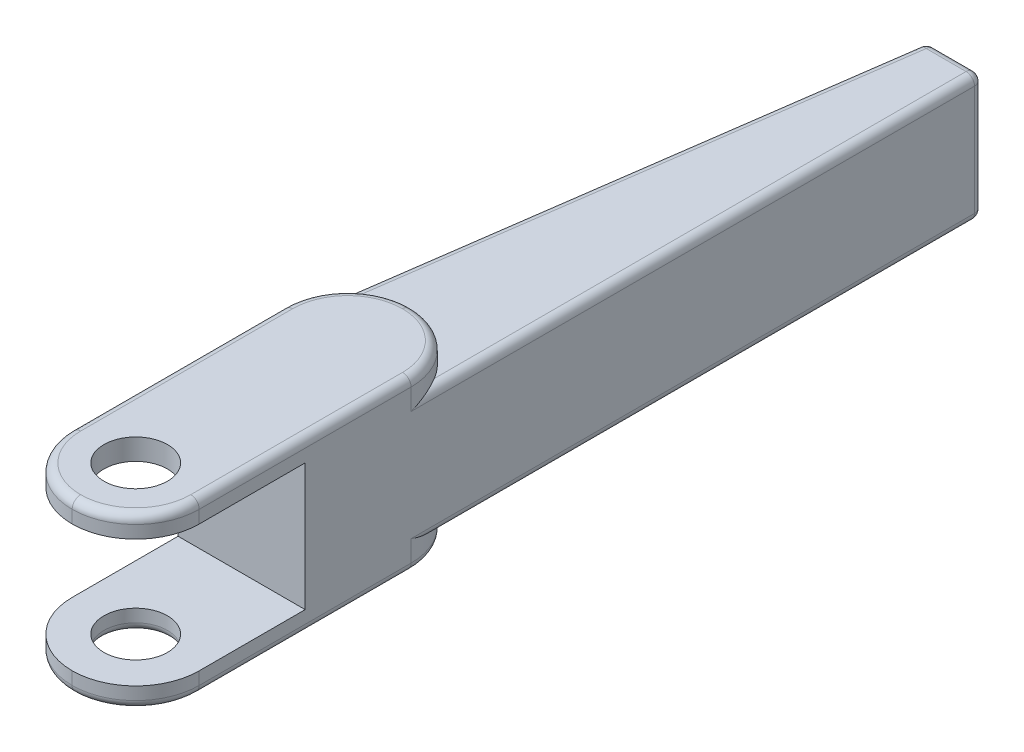
SolidWorks part; units mm, degrees
ref_plane "Front Plane" through (0, 0, 0) normal (0, 0, 1) x (1, 0, 0)
ref_plane "Top Plane" through (0, 0, 0) normal (0, 1, 0) x (1, 0, 0)
ref_plane "Right Plane" through (0, 0, 0) normal (1, 0, 0) x (0, 0, -1)
sketch "Sketch2" plane through (0, 0, 0) normal (0, 0, 1) x (1, 0, 0)
  line L1 (15, 15) -> (-15, 15)
  line L2 (15, 15) -> (15, -15)
  line L3 (15, -15) -> (-15, -15)
  line L4 (-15, 15) -> (-15, -15)
  line L5 (15, 15) -> (-15, -15) construction
  line L6 (15, -15) -> (-15, 15) construction
  point P0 (0, 0)
  dimension "D1" = 30
  dimension "D2" = 30
extrude "Boss-Extrude1" add sketch "Sketch2" along normal blind 160
sketch "Sketch3" plane through (0, 0, 160) normal (0, 0, 1) x (1, 0, 0)
  line L0 (15, 15) -> (-15, 15) construction
  line L1 (15, -20) -> (-15, -20)
  line L2 (15, -20) -> (15, 20)
  line L3 (15, 20) -> (-15, 20)
  line L4 (-15, -20) -> (-15, 20)
  line L5 (15, -20) -> (-15, 20) construction
  line L6 (15, 20) -> (-15, -20) construction
  point P0 (0, 0)
  line M6 (-15, -15) -> (15, -15)
  line M8 (15, 15) -> (-15, 15)
  dimension "D1" = 40
extrude "Boss-Extrude2" add sketch "Sketch3" against normal mid plane 80 contours L4 L2 L3 M8 | L4 L1 L2 M6 region at (0, -17.5, 160) region at (0, 17.5, 160)
fillet "Fillet1" radius 15 8 edges at (15, -17.5, 120) (-15, -17.5, 120) (15, -17.5, 200) (-15, -17.5, 200) (-15, 17.5, 120) (15, 17.5, 120) (-15, 17.5, 200) (15, 17.5, 200)
sketch "Sketch4" plane through (0, 20, 0) normal (0, 1, 0) x (1, 0, 0)
  line L0 (0, -200) -> (0, -185) construction
  line L1 (0, -185) -> (15, -185) construction
  circle A0 centre (0, -185) radius 7.5
  dimension "D1" = 15
extrude "Cut-Extrude1" cut sketch "Sketch4" against normal blind 80
chamfer "Chamfer1" distance 120 angle 8 1 edges at (-15, 0, 0) first distance on face at (-15, 0, 133.3333)
fillet "Fillet2" radius 2 21 edges at (10.6066, 20, 124.3934) (15, 20, 160) (10.6066, 20, 195.6066) (-10.6066, 20, 195.6066) (-15, 20, 160) (-15, -20, 160) (-10.6066, -20, 195.6066) (10.6066, -20, 195.6066) (15, -20, 160) (10.6066, -20, 124.3934) (-10.6066, -20, 124.3934) (0, -20, 192.5) (15, 0, 0) (8.4325, -15, 0) (8.4325, 15, 0) (1.8649, 0, 0) (15, -15, 67.5) (-10.6066, 20, 124.3934) (15, 15, 67.5) (-6.5675, -15, 60) (-6.5675, 15, 60)
